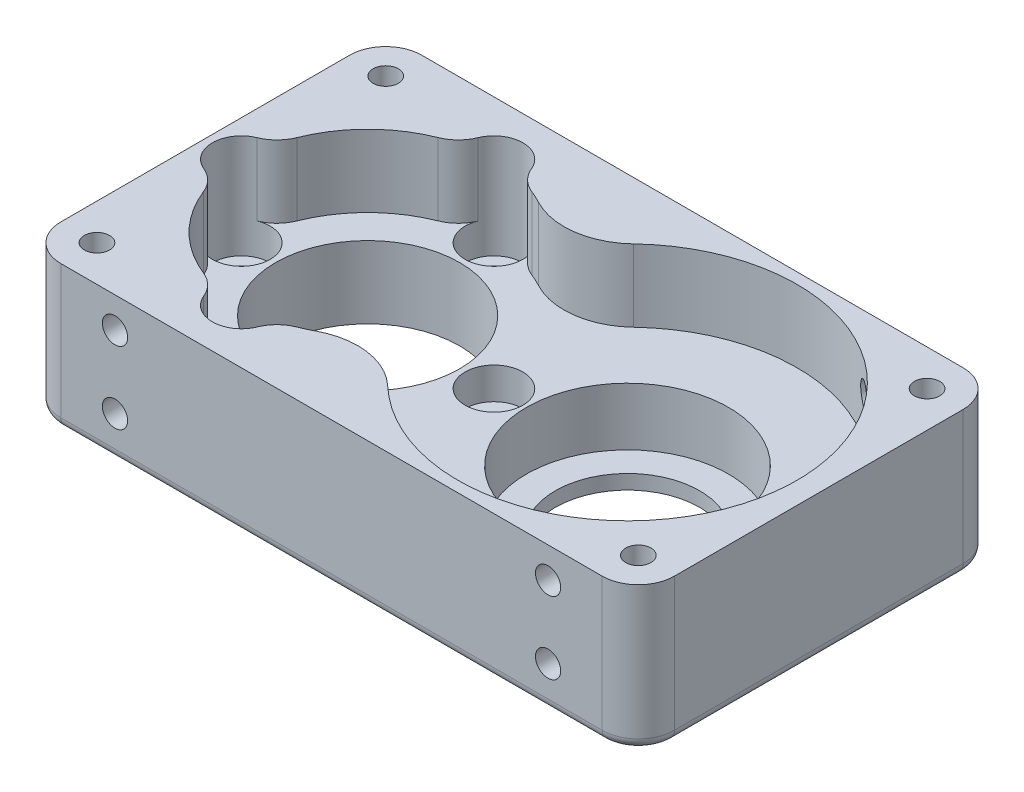
SolidWorks part; units mm, degrees
material "7075-T6 (SN)"
ref_plane "Front Plane" through (0, 0, 0) normal (0, 0, 1) x (1, 0, 0)
ref_plane "Top Plane" through (0, 0, 0) normal (0, 1, 0) x (1, 0, 0)
ref_plane "Right Plane" through (0, 0, 0) normal (1, 0, 0) x (0, 0, -1)
sketch "Sketch1" plane through (0, 0, 0) normal (0, 1, 0) x (1, 0, 0)
  line L1 (-42.5, -25) -> (42.5, -25)
  line L2 (-42.5, -25) -> (-42.5, 25)
  line L3 (-42.5, 25) -> (42.5, 25)
  line L4 (42.5, -25) -> (42.5, 25)
  line L5 (-42.5, -25) -> (42.5, 25) construction
  line L6 (-42.5, 25) -> (42.5, -25) construction
  point P0 (0, 0)
  dimension "D1" = 50
  dimension "D2" = 85
extrude "Boss-Extrude1" add sketch "Sketch1" along normal blind 20
sketch "Sketch2" plane through (0, 20, 0) normal (0, 1, 0) x (1, 0, 0)
  line L0 (-42.5, 0) -> (42.5, 0) construction
  line L1 (-42.5, 25) -> (-42.5, -25) construction
  line L2 (42.5, -25) -> (42.5, 25) construction
  arc A0 (-5.4167, 9.6735) -> (-5.4167, -9.6735) centre (-20, 0) ccw
  arc A1 (-5.4167, -9.6735) -> (-5.4167, 9.6735) centre (16, 0) ccw
  dimension "D1" = 36
  dimension "D2" = 22.5
  dimension "D3" = 35
  dimension "D4" = 47
extrude "Cut-Extrude1" cut sketch "Sketch2" against normal blind 10
fillet "Fillet1" radius 5 4 edges at (42.5, 10, 25) (-42.5, 10, 25) (42.5, 10, -25) (-42.5, 10, -25)
fillet "Fillet2" radius 10 2 edges at (-5.4167, 15, 9.6735) (-5.4167, 15, -9.6735)
sketch "Sketch3" plane through (0, 10, 0) normal (0, 1, 0) x (1, 0, 0)
  circle A0 centre (-20, 0) radius 12.75
  dimension "D1" = 25.5
extrude "Cut-Extrude2" cut sketch "Sketch3" against normal blind 10
sketch "Sketch13" plane through (0, 10, 0) normal (0, 1, 0) x (1, 0, 0)
  circle A0 centre (-20, 0) radius 17.5 construction
  circle A1 centre (-20, 17.5) radius 4
  circle A2 centre (-37.5, 0) radius 4
  circle A3 centre (-20, -17.5) radius 4
  circle A4 centre (-2.5, 0) radius 4
  dimension "D1" = 35
  dimension "D2" = 8
extrude "Cut-Extrude4" cut sketch "Sketch13" along normal blind 10
sketch "Sketch14" plane through (0, 10, 0) normal (0, 1, 0) x (1, 0, 0)
  circle A0 centre (-20, 0) radius 17.5 construction
  dimension "D1" = 35
hole_wizard "CBORE for M4 Hex Socket Head Cap Screw2" positions "Sketch15" profile "Sketch16" counterbore size "M4" standard "DIN" end condition through all
sketch "Sketch15" plane through (0, 10, 0) normal (0, 1, 0) x (1, 0, 0)
  circle A0 centre (-20, 0) radius 17.5 construction
  point P0 (-20, 17.5)
  point P4 (-37.5, 0)
  point P6 (-20, -17.5)
  point P8 (-2.5, 0)
sketch "Sketch16" plane through (-20, 10, -17.5) normal (1, 0, 0) x (0, 0, 1)
  line L0 (0, 0) -> (0, 10)
  line L1 (0, 10) -> (2.25, 10)
  line L3 (2.25, 10) -> (2.25, 4.4)
  line L4 (2.25, 4.4) -> (4, 4.4)
  line L5 (4, 4.4) -> (4, 0)
  line L7 (4, 0) -> (0, 0)
  line L11 (0, -6.35) -> (0, 107.95) construction
  dimension "Thru Hole Dia." = 4.5
  dimension "Thru Hole Depth" = 10
  dimension "C'Bore Dia." = 8
  dimension "C'Bore Depth" = 4.4
fillet "Fillet4" radius 5 6 edges at (-16.0262, 15, 17.0429) (-23.9738, 15, 17.0429) (-37.0429, 15, 3.9738) (-37.0429, 15, -3.9738) (-23.9738, 15, -17.0429) (-16.0262, 15, -17.0429)
sketch "Sketch17" plane through (0, 10, 0) normal (0, 1, 0) x (1, 0, 0)
  circle A0 centre (16, 0) radius 14
  dimension "D1" = 28
extrude "Cut-Extrude5" cut sketch "Sketch17" against normal blind 8
sketch "Sketch18" plane through (0, 2, 0) normal (0, 1, 0) x (1, 0, 0)
  circle A0 centre (16, 0) radius 10
  dimension "D1" = 20
extrude "Cut-Extrude6" cut sketch "Sketch18" against normal blind 6
sketch "Sketch19" plane through (0, 20, 0) normal (0, 1, 0) x (1, 0, 0)
  circle A0 centre (-37.4977, 20) radius 1.75
  circle A1 centre (37.5023, 20) radius 1.75
  circle A2 centre (37.5023, -20) radius 1.75
  circle A3 centre (-37.4977, -20) radius 1.75
  dimension "D1" = 3.5
extrude "Cut-Extrude7" cut sketch "Sketch19" against normal blind 12
fillet "Fillet5" radius 1.5 8 edges at (41.0355, 0, -23.5355) (42.5, 0, 0) (41.0355, 0, 23.5355) (0, 0, 25) (-41.0355, 0, 23.5355) (-42.5, 0, 0) (-41.0355, 0, -23.5355) (0, 0, -25)
sketch "Sketch20" plane through (0, 0, 25) normal (0, 0, 1) x (1, 0, 0)
  line L0 (0, 20) -> (0, 0) construction
  line L1 (-37.5, 20) -> (37.5, 20) construction
  line L2 (-42.5, 10.75) -> (0, 10.75) construction
  line L3 (-42.5, 1.5) -> (-42.5, 20) construction
  line L5 (-30, 5.75) -> (30, 5.75) construction
  line L6 (-30, 5.75) -> (-30, 15.75) construction
  line L7 (-30, 15.75) -> (30, 15.75) construction
  line L8 (30, 5.75) -> (30, 15.75) construction
  line L9 (-30, 5.75) -> (30, 15.75) construction
  line L10 (-30, 15.75) -> (30, 5.75) construction
  circle A0 centre (-30, 15.75) radius 1.75
  circle A1 centre (-30, 5.75) radius 1.75
  circle A2 centre (30, 15.75) radius 1.75
  circle A3 centre (30, 5.75) radius 1.75
  dimension "D3" = 3.5
  dimension "D1" = 10
  dimension "D2" = 60
extrude "Cut-Extrude8" cut sketch "Sketch20" against normal blind 7
ref_plane "Plane1" through (0, 0, 0) normal (0, 0, 1) x (1, 0, 0)
mirror "Mirror1" about plane through (0, 0, 0) normal (0, 0, 1) of "Cut-Extrude8"
